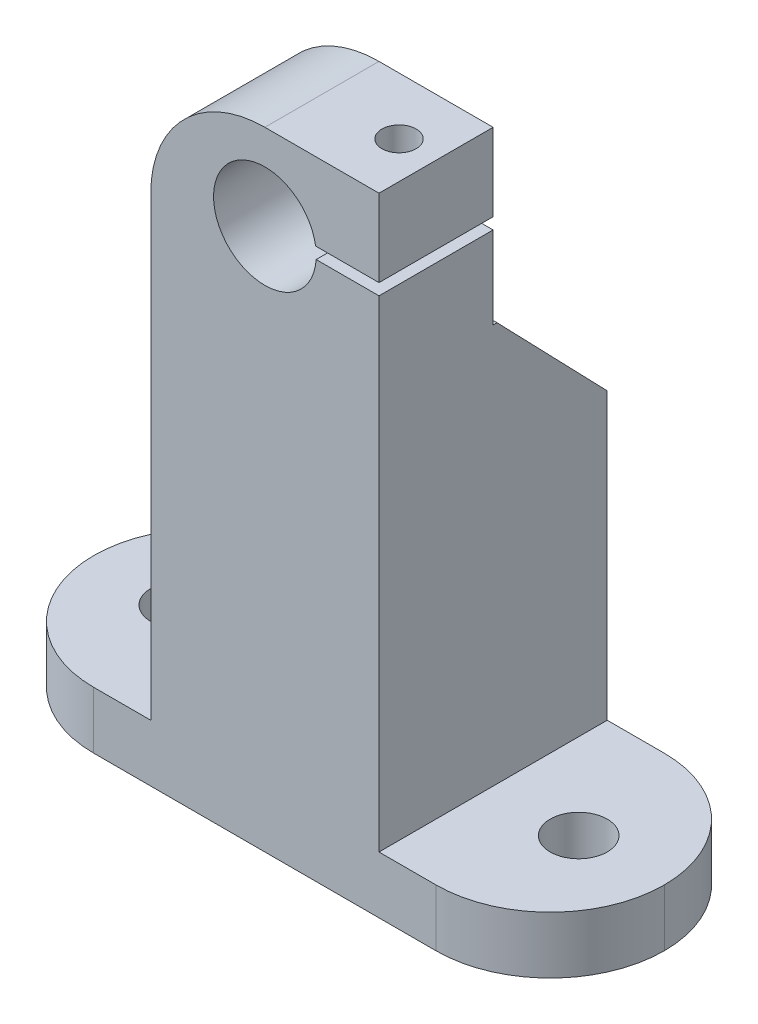
SolidWorks part; units mm, degrees
material "PC/ABS Plastic"
ref_plane "Front Plane" through (0, 0, 0) normal (0, 0, 1) x (1, 0, 0)
ref_plane "Top Plane" through (0, 0, 0) normal (0, 1, 0) x (1, 0, 0)
ref_plane "Right Plane" through (0, 0, 0) normal (1, 0, 0) x (0, 0, -1)
sketch "Esquisse2" plane through (0, 0, 0) normal (0, 0, 1) x (1, 0, 0)
  line L1 (0, 0) -> (20, 0)
  line L2 (0, 0) -> (0, -40)
  line L3 (0, -40) -> (20, -40)
  line L4 (20, 0) -> (20, -40)
  dimension "D1" = 20
  dimension "D2" = 40
extrude "Boss.-Extru.2" add sketch "Esquisse2" along normal blind 20
sketch "Esquisse3" plane through (0, 0, 20) normal (0, 0, 1) x (1, 0, 0)
  line L1 (0, 0) -> (20, 0)
  line L2 (0, 0) -> (0, 15)
  line L3 (0, 15) -> (20, 15)
  line L4 (20, 0) -> (20, 15)
  line L5 (20, 8.2105) -> (13, 8.2105)
  line L6 (20, 8.2105) -> (20, 7.2105)
  line L7 (20, 7.2105) -> (13, 7.2105)
  line L8 (13, 8.2105) -> (13, 7.2105)
  circle A0 centre (10, 7.5) radius 4.5
  line M8 (20, 0) -> (0, 0)
  dimension "D3" = 9
  dimension "D1" = 20
  dimension "D2" = 15
  dimension "D4" = 10
  dimension "D5" = 7.5
  dimension "D6" = 7
  dimension "D7" = 1
extrude "Boss.-Extru.3" add sketch "Esquisse3" against normal blind 10 contours A0 L5 L4 L3 L2 L7 M8 region at (0.25, 7.5, 20)
sketch "Esquisse6" plane through (0, -40, 0) normal (0, -1, 0) x (1, 0, 0)
  line L0 (0, 20) -> (20, 20) construction
  line L1 (-15, 20) -> (35, 20)
  line L2 (-15, 20) -> (-15, 0)
  line L3 (-15, 0) -> (35, 0)
  line L4 (35, 20) -> (35, 0)
  line L5 (0, 0) -> (20, 0) construction
  line L6 (20, 20) -> (20, 0) construction
  line L7 (0, 20) -> (0, 0) construction
  circle A0 centre (-7.5, 10) radius 2.5
  circle A1 centre (27.5, 10) radius 2.5
  dimension "D9" = 5
  dimension "D10" = 5
  dimension "D1" = 0
  dimension "D2" = 0
  dimension "D3" = 15
  dimension "15mm" = 15
  dimension "D4" = 20
  dimension "D5" = 10
  dimension "D6" = 10
  dimension "D7" = 7.5
  dimension "D8" = 7.5
extrude "Boss.-Extru.4" add sketch "Esquisse6" against normal blind 5
sketch "Esquisse8" plane through (0, 15, 0) normal (0, 1, 0) x (1, 0, 0)
  line L0 (0, -10) -> (20, -10) construction
  circle A0 centre (16.7578, -15) radius 1.5
  dimension "D2" = 3
  dimension "D1" = 5
extrude "Enlèv. mat.-Extru.1" cut sketch "Esquisse8" against normal blind 40
fillet "Congé2" radius 10 1 edges at (0, 15, 15)
fillet "Congé3" radius 10 4 edges at (-15, -37.5, 0) (-15, -37.5, 20) (35, -37.5, 20) (35, -37.5, 0)
chamfer "Chanfrein2" distance 10 angle 44 1 edges at (10, 0, 0) first distance on face at (10, -27.5, 0)
